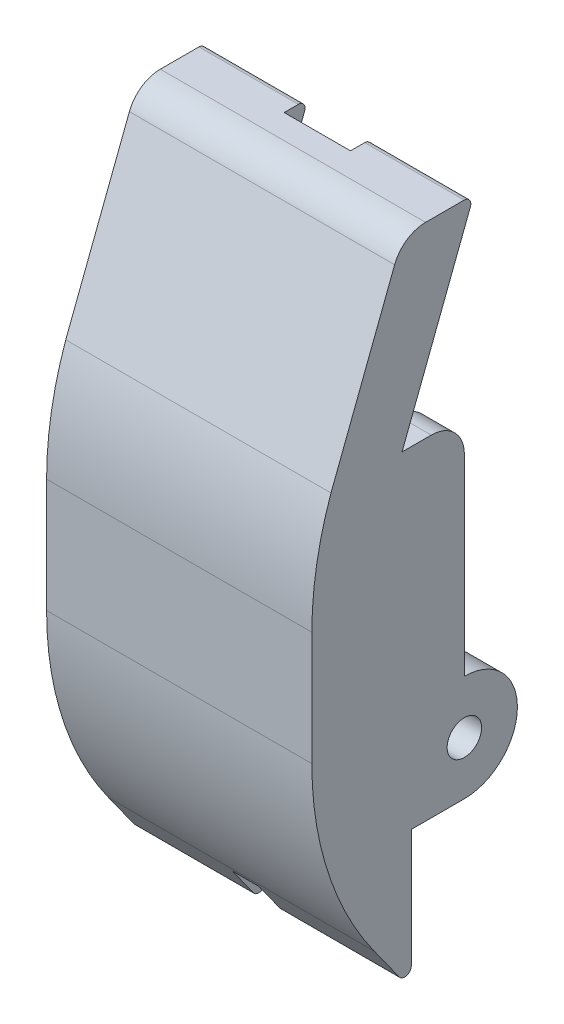
SolidWorks part; units mm, degrees
ref_plane "Front Plane" through (0, 0, 0) normal (0, 0, 1) x (1, 0, 0)
ref_plane "Top Plane" through (0, 0, 0) normal (0, 1, 0) x (1, 0, 0)
ref_plane "Right Plane" through (0, 0, 0) normal (1, 0, 0) x (0, 0, -1)
sketch "Sketch6" plane through (0, 0, 0) normal (1, 0, 0) x (0, 0, -1)
  line L0 (0, 8) -> (0, -8) construction
  line L1 (-23, -8) -> (0, -8)
  line L2 (-23, -8) -> (-23, 42)
  line L5 (0, 8) -> (-13, 8)
  line L6 (-13, 8) -> (-13, 42)
  line L11 (-23, 42) -> (-20.1117, 42)
  line L12 (-20.1117, 42) -> (-9.2835, 70.2083)
  line L13 (-13, 42) -> (-9.4002, 42)
  line L14 (-9.4002, 42) -> (1.4279, 70.2083)
  line L16 (-9.2835, 70.2083) -> (1.4279, 70.2083)
  arc A0 (0, 8) -> (0, -8) centre (0, 0) cw
  circle A1 centre (0, 0) radius 2.6
  point P0 (0, 0)
  dimension "D1" = 5.2
  dimension "D2" = 8
  dimension "D3" = 50
  dimension "D4" = 13
  dimension "D5" = 10
  dimension "D6" = 111
  dimension "D7" = 10
extrude "Boss-Extrude5" add sketch "Sketch6" along normal blind 20 and the other way blind 20
sketch "Sketch7" plane through (0, 8, 0) normal (0, 1, 0) x (1, 0, 0)
  line L1 (-15, -13) -> (15, -13)
  line L2 (-15, -13) -> (-15, 8)
  line L3 (-15, 8) -> (15, 8)
  line L4 (15, -13) -> (15, 8)
  line L5 (20, 8) -> (-20, 8) construction
  line L6 (-20, 0) -> (-20, -13) construction
  line L7 (20, 0) -> (20, -13) construction
  line L8 (-20, -13) -> (20, -13) construction
  point P0 (0, 0)
  dimension "D1" = 5
  dimension "D2" = 5
extrude "Cut-Extrude1" cut sketch "Sketch7" against normal up to surface (16 mm away) up to face at (0, -8, 11.5)
sketch "Sketch9" plane through (20, 0, 0) normal (1, 0, 0) x (0, 0, -1)
  line L0 (-8, -8) -> (-8, -28.8906)
  line L1 (-8, -28.8906) -> (-23, -8)
  line L2 (-23, -8) -> (-8, -8)
  line L3 (-23, -8) -> (0, -8) construction
  dimension "D1" = 15
extrude "Boss-Extrude6" add sketch "Sketch9" against normal offset from surface (18 mm away) 2 up to plane "Right Plane"
mirror "Mirror1" about plane through (0, 0, 0) normal (1, 0, 0) of "Boss-Extrude6"
sketch "Sketch10" plane through (2, 0, 0) normal (-1, 0, 0) x (0, 0, 1)
  line L0 (23, -8) -> (13, -8)
  line L1 (13, -8) -> (13, -21.9271)
  line L2 (13, -21.9271) -> (23, -8)
  line L3 (8, -28.8906) -> (23, -8) construction
extrude "Boss-Extrude7" add sketch "Sketch10" along normal up to surface (4 mm away) up to face at (-2, -13.2227, 13)
sketch "Sketch12" plane through (0, 8, 0) normal (0, 1, 0) x (1, 0, 0)
  line L0 (20, 0) -> (20, -13)
  line L1 (20, -13) -> (15, -13)
  line L2 (15, -13) -> (15, 0)
  line L3 (15, 0) -> (20, 0)
  line L4 (15, -13) -> (20, -13) construction
  line L5 (20, 0) -> (20, -13) construction
  line L6 (15, -13) -> (15, 0) construction
extrude "Boss-Extrude8" add sketch "Sketch12" along normal up to vertex (34 mm away) up to point (20, 42, 13)
mirror "Mirror2" about plane through (0, 0, 0) normal (1, 0, 0) of "Boss-Extrude8"
fillet "Fillet4" radius 5 2 edges at (2, -8, 10.5) (-2, -8, 10.5)
fillet "Fillet5" radius 1 3 edges at (11, -28.8906, 8) (-11, -28.8906, 8) (0, 70.2083, -1.4279)
sketch "Sketch13" plane through (20, 0, 0) normal (1, 0, 0) x (0, 0, -1)
  line L0 (1.4279, 70.2083) -> (-9.4002, 42)
  line L1 (-9.4002, 42) -> (-13.0002, 42)
  line L2 (-13.0002, 42) -> (-2.1721, 70.2083)
  line L3 (-2.1721, 70.2083) -> (1.4279, 70.2083)
  line L4 (-0.0271, 70.2083) -> (-9.2835, 70.2083) construction
  line L5 (-20.1117, 42) -> (-23, 42) construction
  dimension "D1" = 3.6
extrude "Cut-Extrude3" cut sketch "Sketch13" against normal blind 10 from offset 15 offset against normal yes
sketch "Sketch14" plane through (0, 8.5389, 22.2447) normal (0, -0.3584, -0.9336) x (-1, 0, 0)
  line L0 (-15, 35.8416) -> (-5, 48.7949)
  line L2 (-5, 35.8416) -> (-5, 48.7949)
  line L3 (-5, 35.8416) -> (-5, 64.6018) construction
  line L4 (-15, 35.8416) -> (-15, 34.5516)
  line L5 (-15, 34.5516) -> (-5, 34.5516)
  line L6 (-5, 34.5516) -> (-5, 35.8416)
  line L7 (-5, 34.5516) -> (-15, 34.5516) construction
extrude "Cut-Extrude4" cut sketch "Sketch14" against normal up to surface (3.3609 mm away) up to face at (0, 56.1041, 7.5862)
mirror "Mirror3" about plane through (0, 0, 0) normal (1, 0, 0) of "Cut-Extrude4"
fillet "Fillet7" radius 5 5 edges at (0, 70.2083, 9.2835) (-17.5, 42, 0) (17.5, 42, 0) (-5, 54.6952, 6.327) (5, 54.6952, 6.327)
fillet "Fillet8" radius 50 2 edges at (0, 42, 23) (0, -8, 23)
